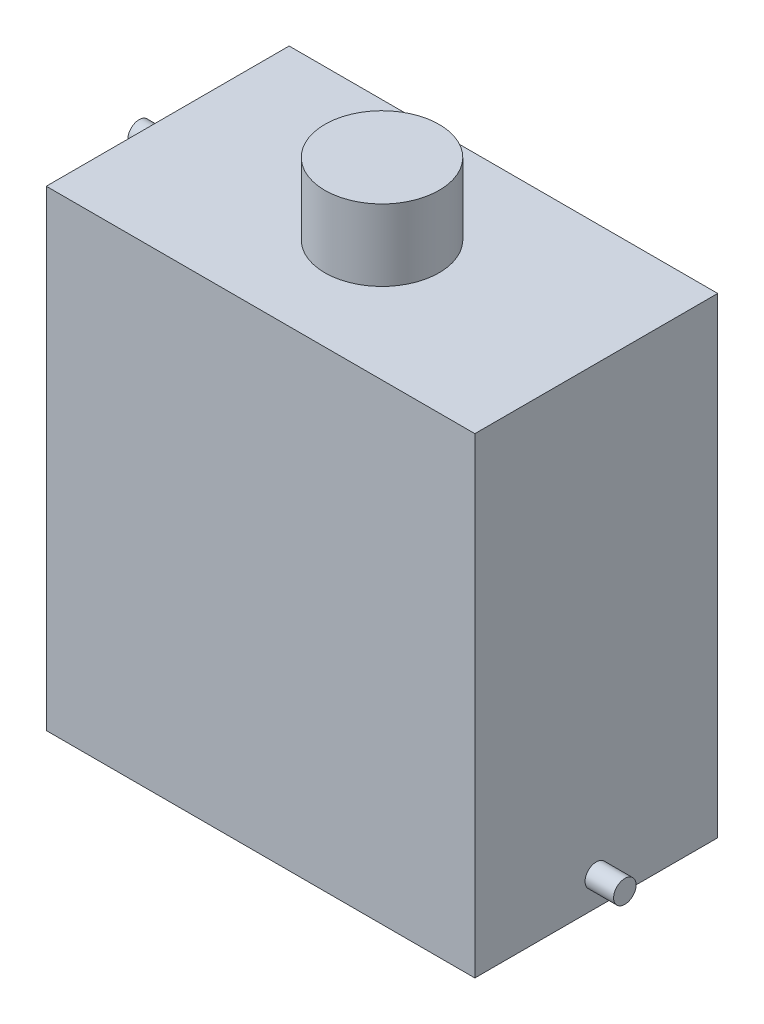
SolidWorks part; units mm, degrees
ref_plane "X-Y Datum" through (0, 0, 0) normal (0, 0, 1) x (1, 0, 0)
ref_plane "X-Z Datum" through (0, 0, 0) normal (0, 1, 0) x (1, 0, 0)
ref_plane "Y-Z Datum" through (0, 0, 0) normal (1, 0, 0) x (0, 0, -1)
sketch "Sketch1" plane through (0, 0, 0) normal (0, 1, 0) x (1, 0, 0)
  line L1 (95.25, 53.975) -> (-95.25, 53.975)
  line L2 (95.25, 53.975) -> (95.25, -53.975)
  line L3 (95.25, -53.975) -> (-95.25, -53.975)
  line L4 (-95.25, 53.975) -> (-95.25, -53.975)
  line L5 (95.25, 53.975) -> (-95.25, -53.975) construction
  line L6 (95.25, -53.975) -> (-95.25, 53.975) construction
  point P0 (0, 0)
  dimension "D1" = 190.5
  dimension "D2" = 107.95
extrude "Boss-Extrude1" add sketch "Sketch1" along normal blind 209.55
sketch "Sketch2" plane through (0, 209.55, 0) normal (0, 1, 0) x (1, 0, 0)
  circle A0 centre (0, 0) radius 25.4
  dimension "D1" = 50.8
extrude "Boss-Extrude2" add sketch "Sketch2" along normal blind 31.75
sketch "Sketch3" plane through (-95.25, 0, 0) normal (-1, 0, 0) x (0, 0, 1)
  line L0 (-53.975, 209.55) -> (53.975, 209.55) construction
  line L1 (-53.975, 209.55) -> (53.975, 209.55) construction
  line L2 (0, 209.55) -> (0, 0) construction
  line L3 (-53.975, 0) -> (53.975, 0) construction
  circle A0 centre (0, 196.85) radius 5
  dimension "D2" = 10
  dimension "D1" = 12.7
extrude "Boss-Extrude3" add sketch "Sketch3" along normal blind 12.7
sketch "Sketch5" plane through (95.25, 0, 0) normal (1, 0, 0) x (0, 0, -1)
  line L0 (-53.975, 0) -> (53.975, 0) construction
  line L1 (-53.975, 0) -> (53.975, 0) construction
  line L2 (0, 0) -> (0, 209.55) construction
  line L3 (-53.975, 209.55) -> (53.975, 209.55) construction
  circle A0 centre (0, 12.7) radius 5
  dimension "D1" = 10
  dimension "D2" = 12.7
extrude "Boss-Extrude4" add sketch "Sketch5" along normal blind 12.7
